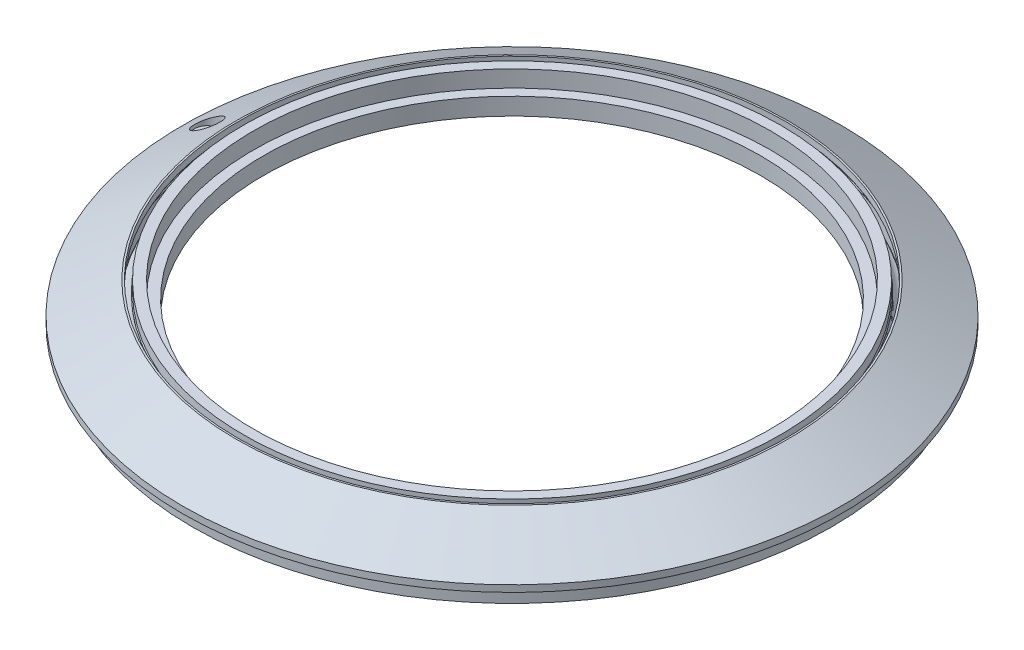
SolidWorks part; units mm, degrees
material "AISI Type A2 Tool Steel"
ref_plane "Front Plane" through (0, 0, 0) normal (0, 0, 1) x (1, 0, 0)
ref_plane "Top Plane" through (0, 0, 0) normal (0, 1, 0) x (1, 0, 0)
ref_plane "Right Plane" through (0, 0, 0) normal (1, 0, 0) x (0, 0, -1)
ref_axis "Centarus" through (0, -46.8246, 0) along (0, 1, 0)
sketch "Sketch1" plane through (0, 0, 0) normal (0, 0, 1) x (1, 0, 0)
  line L0 (0, 0) -> (0, 29.8552) construction
  line L1 (-99.4641, 7) -> (-99.4641, 5)
  line L2 (0, 0) -> (-96.4641, 0) construction
  line L3 (-99.4641, 7) -> (-83.2679, 16.3509)
  line L4 (-84, 8.1547) -> (-81, 13.3509)
  line L5 (-82.7321, 14.3509) -> (-85.7321, 9.1547)
  line L6 (-83.2679, 16.3509) -> (-82.7321, 16.3509)
  line L7 (-82.7321, 16.3509) -> (-82.7321, 14.3509)
  line L8 (-85.7321, 9.1547) -> (-87.4641, 8.1547)
  line L9 (-99.4641, 5) -> (-96.4641, 5)
  line L10 (-96.4641, 5) -> (-96.4641, 0)
  line L11 (-87.4641, 8.1547) -> (-87.4641, 0)
  line L12 (-84.2321, 11.7528) -> (-82.5, 10.7528) construction
  line L13 (-81, 13.3509) -> (-81, 16.3509)
  line L14 (-81, 16.3509) -> (-78, 16.3509)
  line L15 (-78, 16.3509) -> (-78, 11.3509)
  line L16 (-78, 11.3509) -> (-75, 11.3509)
  line L17 (-75, 11.3509) -> (-75, 6.1547)
  line L18 (-75, 6.1547) -> (-84, 6.1547)
  line L19 (-84, 6.1547) -> (-84, 8.1547)
  line L20 (-83.366, 11.2528) -> (-69.0903, 35.9791) construction
  line L21 (-96.4641, 0) -> (-87.4641, 0)
  line L23 (-77.8, 11.3509) -> (0, 11.3509)
  line L24 (-77.8, 11.3509) -> (-77.8, 16.3509)
  line L25 (-77.8, 16.3509) -> (0, 16.3509)
  line L26 (0, 11.3509) -> (0, 16.3509)
  arc A0 (-85.4821, 9.5877) -> (-82.9821, 13.9178) centre (-81.9587, 10.4403) cw
  arc A1 (-83.75, 8.5877) -> (-81.25, 12.9178) centre (-84.7733, 12.0653) ccw
  circle A2 centre (-83.366, 11.2528) radius 2 construction
  dimension "D14" = 4
  dimension "D1" = 30
  dimension "D2" = 2
  dimension "D3" = 5
  dimension "D4" = 5
  dimension "D5" = 3
  dimension "D6" = 9
  dimension "D7" = 2
  dimension "D8" = 120
  dimension "D9" = 6
  dimension "D10" = 2
  dimension "D11" = 5
  dimension "D12" = 3
  dimension "D13" = 2
  dimension "D15" = 150
  dimension "D16" = 0.5
  dimension "D17" = 2
  dimension "D18" = 3
  dimension "D19" = 22.7017
  dimension "D20" = 0.2
revolve "Revolve1" add sketch "Sketch1" angle 360 about L0 region at (-91.1631, 6.8159, 0)
sketch "Sketch2" plane through (0, 0, 0) normal (0, -1, 0) x (1, 0, 0)
  line L1 (-96.4641, 0) -> (-87.4641, 0) construction
  circle A0 centre (-91.9641, 0) radius 2
  circle A1 centre (0, 0) radius 96.4641 construction
  circle A2 centre (0, 0) radius 87.4641 construction
  circle A4 centre (-91.9641, 0) radius 3.8
  point P11 (-91.9641, 0)
  dimension "D1" = 4
  dimension "D2" = 7.6
extrude "Cut-Extrude1" cut sketch "Sketch2" against normal up to next contours A0
extrude "Cut-Extrude5" cut sketch "Sketch2<3>" against normal blind 10 from offset 8 contours A4 offset against normal yes
sketch "Sketch2<3>" plane through (0, 0, 0) normal (0, -1, 0) x (1, 0, 0) same geometry as "Sketch2"
revolve "Revolve2" add sketch "Sketch1<3>" angle 360 about L0 region at (-79.1748, 9.9829, 0)
sketch "Sketch1<3>" plane through (0, 0, 0) normal (0, 0, 1) x (1, 0, 0) same geometry as "Sketch1"
